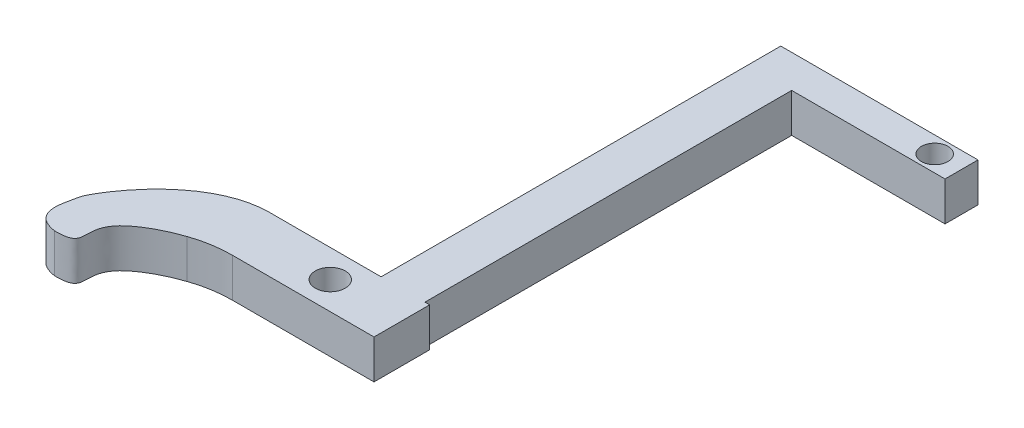
SolidWorks part; units mm, degrees
ref_plane "Front Plane" through (0, 0, 0) normal (0, 0, 1) x (1, 0, 0)
ref_plane "Top Plane" through (0, 0, 0) normal (0, 1, 0) x (1, 0, 0)
ref_plane "Right Plane" through (0, 0, 0) normal (1, 0, 0) x (0, 0, -1)
sketch "Sketch2" plane through (0, 0, 0) normal (0, 1, 0) x (1, 0, 0)
  line L0 (19.1234, 25.7011) -> (34.5975, 25.7011)
  line L2 (19.1234, 25.7011) -> (19.1234, 20.1324)
  line L3 (19.1234, 20.1324) -> (34.5975, 20.1324)
  line L4 (34.5975, 25.7011) -> (34.5975, 20.1324)
  line L9 (27.4344, 25.7011) -> (27.4344, 20.1324) construction
  line L10 (29.7385, 25.7011) -> (34.1286, 25.7011)
  line L11 (29.7385, 25.7011) -> (29.7385, 65.7011)
  line L12 (29.7385, 65.7011) -> (34.1286, 65.7011)
  line L13 (34.1286, 25.7011) -> (34.1286, 65.7011)
  circle A0 centre (27.4344, 22.9167) radius 1.5
  spline S0 degree 3 poles (19.1234, 20.1324) (16.216, 19.6759) (8.7178, 15.9482) (12.7758, 13.3099) (9.3947, 13.3427) knots 0 0 0 0 0.36869 1 1 1 1
  spline S1 degree 3 poles (9.3947, 13.3427) (6.7943, 13.7761) (7.4237, 16.0946) (7.9611, 18.6182) (13.1668, 25.9747) (19.1234, 25.7011) knots 0 0 0 0 0.58065 0.68065 1 1 1 1
  point P15 (27.4676, 21.9182)
  dimension "D2" = 3
  dimension "D1" = 40
extrude "Boss-Extrude1" add sketch "Sketch2" along normal blind 3.9 contours L4 L0 L2 L3 A0 | S1 S0 L2 | L0 | L0 | L9 L0 L2 L3 A0 region at (22.988, 0, -22.9167) region at (13.2343, 0, -20.0496) region at (31.3023, 0, -22.9167) region at (31.9336, 0, -45.7011)
fillet "Fillet3" radius 12 2 edges at (19.1234, 1.95, -25.7011) (19.1234, 1.95, -20.1324)
sketch "Sketch3" plane through (0, 3.9, 0) normal (0, 1, 0) x (1, 0, 0)
  line L0 (46.7914, 65.7011) -> (46.7914, 62.4008) construction
  line L1 (29.7385, 65.7011) -> (49.4757, 65.7011)
  line L2 (29.7385, 65.7011) -> (29.7385, 62.4008)
  line L3 (29.7385, 62.4008) -> (49.4757, 62.4008)
  line L4 (49.4757, 65.7011) -> (49.4757, 62.4008)
  circle A0 centre (46.7914, 64.0509) radius 1.3254
  point P9 (43.3753, 64.0509)
  dimension "D1" = 2.6843
extrude "Boss-Extrude2" add sketch "Sketch3" against normal up to surface (3.9 mm away) up to face at (27.4344, 0, -21.4167)
